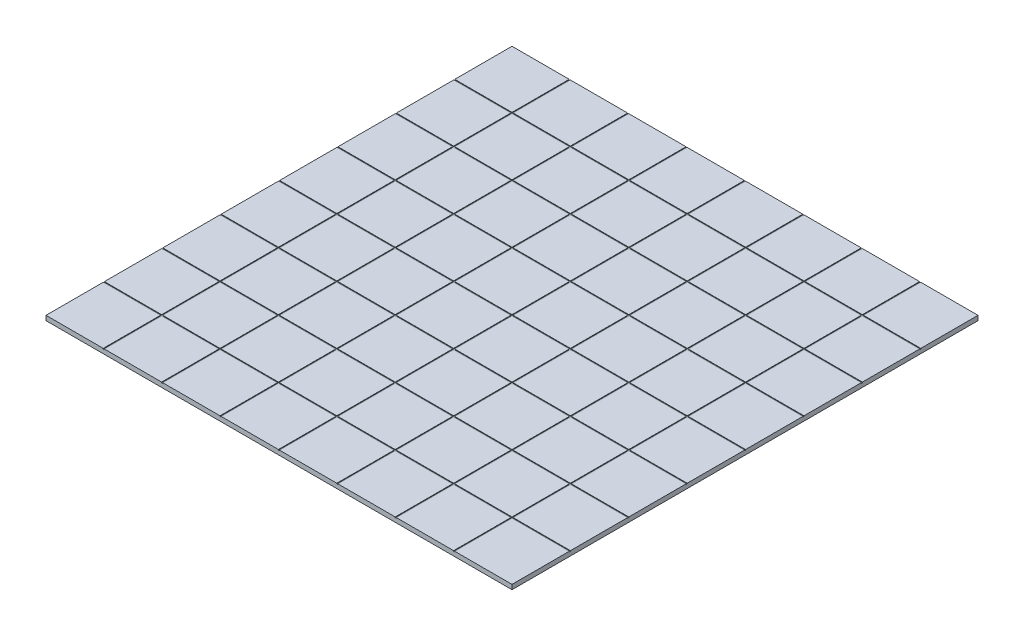
SolidWorks part; units mm, degrees
ref_plane "Front Plane" through (0, 0, 0) normal (0, 0, 1) x (1, 0, 0)
ref_plane "Top Plane" through (0, 0, 0) normal (0, 1, 0) x (1, 0, 0)
ref_plane "Right Plane" through (0, 0, 0) normal (1, 0, 0) x (0, 0, -1)
sketch "Sketch1" plane through (0, 0, 0) normal (0, 1, 0) x (1, 0, 0)
  line L1 (0, 0) -> (200, 0)
  line L2 (0, 0) -> (0, 200)
  line L3 (0, 200) -> (200, 200)
  line L4 (200, 0) -> (200, 200)
  dimension "D1" = 200
  dimension "D2" = 200
extrude "Boss-Extrude1" add sketch "Sketch1" along normal blind 2
sketch "Sketch2" plane through (0, 2, 0) normal (0, 1, 0) x (1, 0, 0)
  line L0 (200, 200) -> (0, 200) construction
  line L1 (24.5625, 200) -> (25.0625, 200)
  line L2 (24.5625, 200) -> (24.5625, 0)
  line L3 (24.5625, 0) -> (25.0625, 0)
  line L4 (25.0625, 200) -> (25.0625, 0)
  line L5 (0, 0) -> (200, 0) construction
  line L6 (200, 0) -> (200, 200) construction
  line L7 (49.625, 0) -> (50.125, 0)
  line L8 (49.625, 0) -> (49.625, 200)
  line L9 (49.625, 200) -> (50.125, 200)
  line L10 (50.125, 0) -> (50.125, 200)
  line L11 (99.75, 0) -> (100.25, 0)
  line L12 (99.75, 0) -> (99.75, 200)
  line L13 (99.75, 200) -> (100.25, 200)
  line L14 (100.25, 0) -> (100.25, 200)
  line L15 (74.6875, 0) -> (75.1875, 0)
  line L16 (74.6875, 0) -> (74.6875, 200)
  line L17 (74.6875, 200) -> (75.1875, 200)
  line L18 (75.1875, 0) -> (75.1875, 200)
  line L19 (124.8125, 0) -> (125.3125, 0)
  line L20 (124.8125, 0) -> (124.8125, 200)
  line L21 (124.8125, 200) -> (125.3125, 200)
  line L22 (125.3125, 0) -> (125.3125, 200)
  line L23 (149.875, 0) -> (150.375, 0)
  line L24 (149.875, 0) -> (149.875, 200)
  line L25 (149.875, 200) -> (150.375, 200)
  line L26 (150.375, 0) -> (150.375, 200)
  line L27 (174.9375, 0) -> (175.4375, 0)
  line L28 (174.9375, 0) -> (174.9375, 200)
  line L29 (174.9375, 200) -> (175.4375, 200)
  line L30 (175.4375, 0) -> (175.4375, 200)
  line L31 (0, 200) -> (0, 0) construction
  line L33 (0, 175.4375) -> (200, 175.4375)
  line L34 (0, 175.4375) -> (0, 174.9375)
  line L35 (0, 174.9375) -> (200, 174.9375)
  line L36 (200, 175.4375) -> (200, 174.9375)
  line L37 (0, 150.375) -> (200, 150.375)
  line L38 (0, 150.375) -> (0, 149.875)
  line L39 (0, 149.875) -> (200, 149.875)
  line L40 (200, 150.375) -> (200, 149.875)
  line L41 (0, 125.3125) -> (200, 125.3125)
  line L42 (0, 125.3125) -> (0, 124.8125)
  line L43 (0, 124.8125) -> (200, 124.8125)
  line L44 (200, 125.3125) -> (200, 124.8125)
  line L45 (0, 100.25) -> (200, 100.25)
  line L46 (0, 100.25) -> (0, 99.75)
  line L47 (0, 99.75) -> (200, 99.75)
  line L48 (200, 100.25) -> (200, 99.75)
  line L49 (0, 75.1875) -> (200, 75.1875)
  line L50 (0, 75.1875) -> (0, 74.6875)
  line L51 (0, 74.6875) -> (200, 74.6875)
  line L52 (200, 75.1875) -> (200, 74.6875)
  line L53 (0, 50.125) -> (200, 50.125)
  line L54 (0, 50.125) -> (0, 49.625)
  line L55 (0, 49.625) -> (200, 49.625)
  line L56 (200, 50.125) -> (200, 49.625)
  line L57 (0, 25.0625) -> (200, 25.0625)
  line L58 (0, 25.0625) -> (0, 24.5625)
  line L59 (0, 24.5625) -> (200, 24.5625)
  line L60 (200, 25.0625) -> (200, 24.5625)
  line M29 (0, 200) -> (0, 0)
  dimension "D1" = 0.5
  dimension "D2" = 0.5
  dimension "D3" = 0.5
  dimension "D4" = 0.5
  dimension "D5" = 0.5
  dimension "D6" = 0.5
  dimension "D7" = 0.5
  dimension "D8" = 24.5625
  dimension "D9" = 0.5
  dimension "D10" = 24.5625
  dimension "D11" = 24.5625
  dimension "D12" = 24.5625
  dimension "D13" = 24.5625
  dimension "D14" = 24.5625
  dimension "D15" = 24.5625
  dimension "D16" = 24.5625
  dimension "D17" = 0.5
  dimension "D18" = 24.5625
  dimension "D19" = 0.5
  dimension "D20" = 24.5625
  dimension "D21" = 0.5
  dimension "D22" = 24.5625
  dimension "D23" = 0.5
  dimension "D24" = 24.5625
  dimension "D25" = 0.5
  dimension "D26" = 24.5625
  dimension "D27" = 0.5
  dimension "D28" = 24.5625
  dimension "D29" = 0.5
  dimension "D30" = 24.5625
  dimension "D31" = 24.5625
extrude "Cut-Extrude1" cut sketch "Sketch2" against normal blind 0.25 contours L51 L2 L49 M29 | L2 L3 L4 L1 | L49 L52 L51 L50 | L57 L60 L59 L58 | L55 L56 L53 L54 | L47 L48 L45 L46 | L41 L44 L43 L42 | L39 L40 L37 L38 | L33 L36 L35 L34 | L8 L9 L10 L7 | L18 L17 L16 L15 | L12 L13 L14 L11 | L20 L21 L22 L19 | L26 L25 L24 L23 | L30 L29 L28 L27 region at (12.2813, 2, -74.9375)
